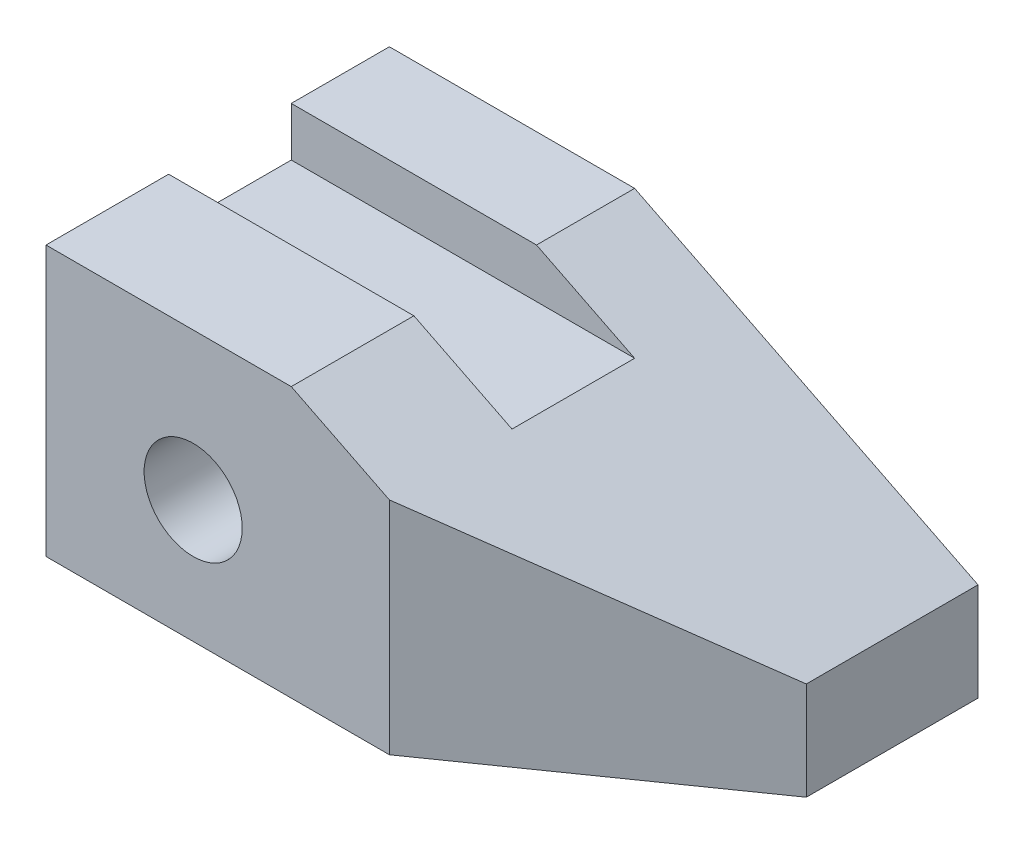
SolidWorks part; units mm, degrees
material "Zinc AC41A Alloy, As Cast"
ref_plane "Front Plane" through (0, 0, 0) normal (0, 0, 1) x (1, 0, 0)
ref_plane "Top Plane" through (0, 0, 0) normal (0, 1, 0) x (1, 0, 0)
ref_plane "Right Plane" through (0, 0, 0) normal (1, 0, 0) x (0, 0, -1)
ref_axis "X-axis" through (-88.99, 0, 0) along (1, 0, 0)
ref_axis "Y-axis" through (0, 55, 0) along (0, -1, 0)
ref_axis "Z-axis" through (0, 0, -88.99) along (0, 0, 1)
sketch "Sketch1" plane through (0, 0, 0) normal (0, 0, 1) x (1, 0, 0)
  line L0 (0, 0) -> (0, 69.85)
  line L1 (0, 69.85) -> (63.5, 69.85)
  line L2 (63.5, 69.85) -> (88.9, 57.15)
  line L3 (88.9, 57.15) -> (152.4, 25.4)
  line L4 (152.4, 25.4) -> (152.4, 0)
  line L5 (152.4, 0) -> (0, 0)
  dimension "D1" = 88.9
  dimension "D2" = 25.4
  dimension "D3" = 63.5
  dimension "D4" = 69.85
  dimension "D5" = 152.4
extrude "Boss-Extrude1" add sketch "Sketch1" along normal mid plane 88.9
sketch "Sketch2" plane through (0, 69.85, 0) normal (0, 1, 0) x (1, 0, 0)
  line L0 (0, -44.45) -> (0, 44.45) construction
  line L1 (0, 19.05) -> (88.9, 19.05)
  line L2 (0, 19.05) -> (0, -12.7)
  line L3 (0, -12.7) -> (88.9, -12.7)
  line L4 (88.9, 19.05) -> (88.9, -12.7)
  line L5 (63.5, 44.45) -> (0, 44.45) construction
  dimension "D1" = 88.9
  dimension "D2" = 31.75
  dimension "D3" = 25.4
extrude "Cut-Extrude1" cut sketch "Sketch2" against normal blind 12.7
sketch "Sketch3" plane through (0, 0, 0) normal (0, 1, 0) x (1, 0, 0)
  line L6 (88.9, -44.45) -> (152.4, 0)
  line L7 (152.4, -44.45) -> (63.5, -44.45) construction
  line L8 (152.4, -44.45) -> (152.4, 44.45) construction
  line L9 (152.4, 0) -> (152.4, -44.45)
  line L10 (152.4, -44.45) -> (88.9, -44.45)
  dimension "D1" = 88.9
extrude "Cut-Extrude2" cut sketch "Sketch3" along normal through all
hole_wizard "1/4 (1) Diameter Hole1" positions "Sketch4" profile "Sketch5" hole size "1/4" standard "ANSI Inch" end condition through all
sketch "Sketch4" plane through (0, 0, 44.45) normal (0, 0, 1) x (1, 0, 0)
  line L0 (0, 0) -> (88.9, 0) construction
  line L1 (0, 69.85) -> (0, 0) construction
  point P0 (38.1, 31.75)
  dimension "D1" = 31.75
  dimension "D2" = 38.1
sketch "Sketch5" plane through (38.1, 31.75, 44.45) normal (1, 0, 0) x (0, -1, 0)
  line L0 (0, 0) -> (0, 88.9)
  line L1 (0, 88.9) -> (12.7, 88.9)
  line L2 (12.7, 88.9) -> (12.7, 0)
  line L5 (12.7, 0) -> (0, 0)
  line L11 (0, -6.35) -> (0, 107.95) construction
  dimension "Thru Hole Dia." = 25.4
  dimension "Thru Hole Depth" = 88.9
